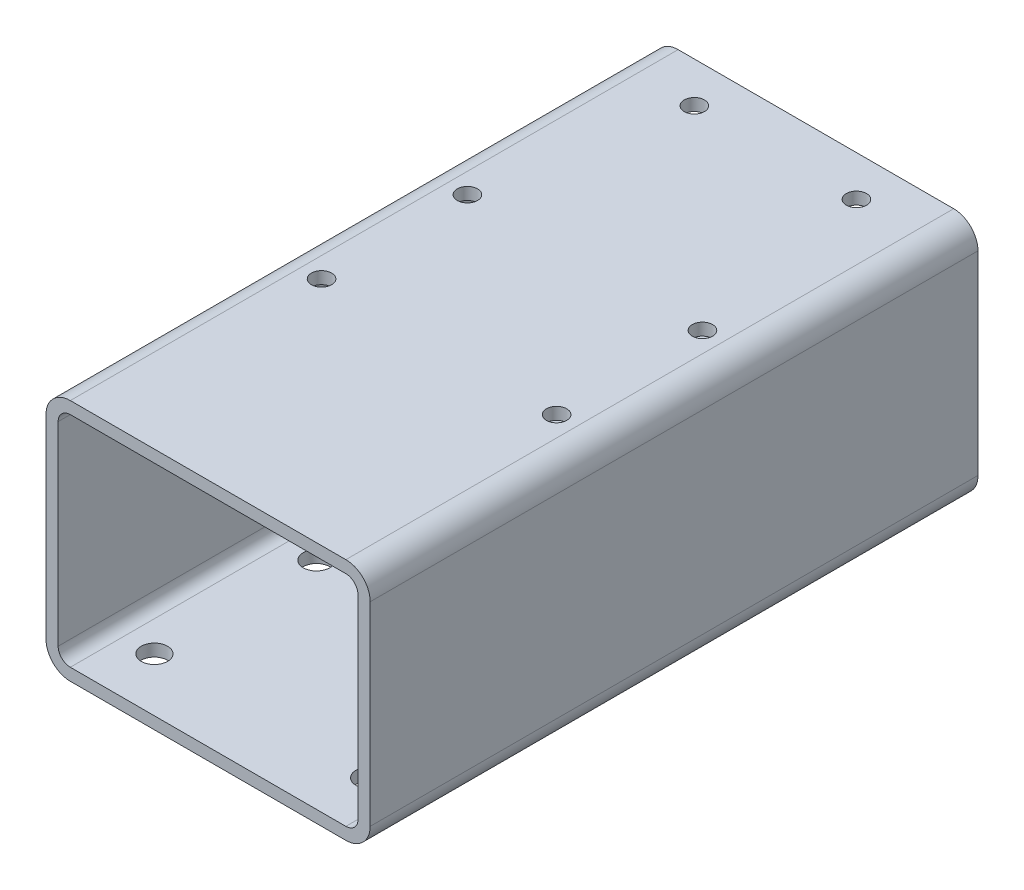
SolidWorks part; units mm, degrees
ref_plane "Front Plane" through (0, 0, 0) normal (0, 0, 1) x (1, 0, 0)
ref_plane "Top Plane" through (0, 0, 0) normal (0, 1, 0) x (1, 0, 0)
ref_plane "Right Plane" through (0, 0, 0) normal (1, 0, 0) x (0, 0, -1)
sketch "Sketch1" plane through (0, 0, 0) normal (0, 0, 1) x (1, 0, 0)
  line L0 (-34, 27) -> (34, 27)
  line L1 (-34, -30) -> (34, -30)
  line L2 (-40, -24) -> (-40, 24)
  line L3 (-34, 30) -> (34, 30)
  line L4 (40, -24) -> (40, 24)
  line L5 (-40, -30) -> (40, 30) construction
  line L6 (-40, 30) -> (40, -30) construction
  line L7 (37, -24) -> (37, 24)
  line L8 (-34, -27) -> (34, -27)
  line L9 (-37, -24) -> (-37, 24)
  arc A0 (-40, 24) -> (-34, 30) centre (-34, 24) cw
  arc A1 (-34, -30) -> (-40, -24) centre (-34, -24) cw
  arc A2 (34, -30) -> (40, -24) centre (34, -24) ccw
  arc A3 (40, 24) -> (34, 30) centre (34, 24) ccw
  arc A4 (37, 24) -> (34, 27) centre (34, 24) ccw
  arc A5 (34, -27) -> (37, -24) centre (34, -24) ccw
  arc A6 (-34, -27) -> (-37, -24) centre (-34, -24) cw
  arc A7 (-37, 24) -> (-34, 27) centre (-34, 24) cw
  point P0 (0, 0)
  dimension "D1" = 6
  dimension "D2" = 6
  dimension "D3" = 60
  dimension "D4" = 80
  dimension "D5" = 3
extrude "Boss-Extrude1" add sketch "Sketch1" along normal blind 75 and the other way blind 75
sketch "Sketch2" plane through (0, -30, 0) normal (0, -1, 0) x (1, 0, 0)
  line L0 (-34, 0) -> (34, 0) construction
  line L1 (-34, -75) -> (-34, 75) construction
  line L2 (34, -75) -> (34, 75) construction
  line L4 (-26.5, 61.75) -> (26.5, 61.75) construction
  line L5 (-26.5, 61.75) -> (-26.5, 21.75) construction
  line L6 (-26.5, 21.75) -> (26.5, 21.75) construction
  line L7 (26.5, 61.75) -> (26.5, 21.75)
  line L9 (0, 61.75) -> (0, 75) construction
  line L10 (-34, 75) -> (34, 75) construction
  line L11 (0, -61.75) -> (0, -75) construction
  line L12 (-26.5, -21.75) -> (26.5, -21.75) construction
  line L13 (-26.5, -61.75) -> (-26.5, -21.75) construction
  line L14 (-26.5, -61.75) -> (26.5, -61.75) construction
  line L15 (26.5, -61.75) -> (26.5, -21.75)
  dimension "D1" = 40
  dimension "D2" = 53
  dimension "D3" = 13.25
hole_wizard "Ø6.5 (6.5) Diameter Hole1" positions "3DSketch1" profile "Sketch3" hole size "Ø6.5" standard "ANSI Metric" end condition up to next
sketch3d "3DSketch1"
  point P0 (-26.5, -30, 61.75)
  point P3 (26.5, -30, 61.75)
  point P6 (26.5, -30, 21.75)
  point P9 (-26.5, -30, 21.75)
  point P12 (-26.5, -30, -21.75)
  point P15 (26.5, -30, -21.75)
  point P18 (26.5, -30, -61.75)
  point P21 (-26.5, -30, -61.75)
sketch "Sketch3" plane through (-26.5, -30, 61.75) normal (1, 0, 0) x (0, 0, -1)
  line L0 (0, 0) -> (0, 3)
  line L1 (0, 3) -> (3.25, 3)
  line L2 (3.25, 3) -> (3.25, 0)
  line L5 (3.25, 0) -> (0, 0)
  line L11 (0, -6.35) -> (0, 107.95) construction
  dimension "Thru Hole Dia." = 6.5
  dimension "Thru Hole Depth" = 3
sketch "Sketch4" plane through (0, 30, 0) normal (0, 1, 0) x (1, 0, 0)
  line L0 (-660, -24) -> (40, -24) construction
  line L1 (40, -24) -> (40, 24) construction
  line L2 (40, 24) -> (-660, 24) construction
  line L3 (-660, 24) -> (-660, -24) construction
  line L4 (-34, 75) -> (-34, -75)
  line L5 (-34, -75) -> (34, -75)
  line L6 (34, -75) -> (34, 75)
  line L7 (34, 75) -> (-34, 75)
  line L8 (-34, 75) -> (-34, -75)
  line L9 (-34, -75) -> (34, -75)
  line L10 (34, -75) -> (34, 75)
  line L11 (34, 75) -> (-34, 75)
  line L12 (-35, 45) -> (35, 45)
  line L13 (35, 45) -> (35, 75)
  line L14 (35, 75) -> (-35, 75)
  line L15 (-35, 75) -> (-35, 45)
  line L16 (-35, 45) -> (35, 45)
  line L17 (35, 45) -> (35, 75)
  line L18 (35, 75) -> (-35, 75)
  line L19 (-35, 75) -> (-35, 45)
  line L20 (-35, 45) -> (35, 45) construction
  line L21 (35, 45) -> (35, 75) construction
  line L22 (35, 75) -> (-35, 75) construction
  line L23 (-35, 75) -> (-35, 45) construction
  line L24 (-660, -24) -> (40, -24)
  line L25 (40, -24) -> (40, 24)
  line L26 (40, 24) -> (-660, 24)
  line L27 (-660, 24) -> (-660, -24)
  line L28 (-35, 45) -> (35, 45)
  line L29 (35, 45) -> (35, 75)
  line L30 (35, 75) -> (-35, 75)
  line L31 (-35, 75) -> (-35, 45)
  circle A1 centre (-591, 18) radius 3.25
  circle A2 centre (-591, 18) radius 3.25
  circle A3 centre (-649, -18) radius 3.25
  circle A4 centre (-649, -18) radius 3.25
  circle A5 centre (-29, -18) radius 3.25
  circle A6 centre (-29, -18) radius 3.25
  circle A7 centre (29, 18) radius 3.25
  circle A8 centre (29, 18) radius 3.25
  circle A9 centre (29, -18) radius 3.25
  circle A10 centre (29, -18) radius 3.25
  circle A11 centre (-29, 18) radius 3.25
  circle A12 centre (-29, 18) radius 3.25
  circle A13 centre (-649, 18) radius 3.25
  circle A14 centre (-649, 18) radius 3.25
  circle A15 centre (-591, -18) radius 3.25
  circle A16 centre (-591, -18) radius 3.25
  circle A17 centre (-20, 65) radius 3.25
  circle A18 centre (-20, 65) radius 3.25
  circle A19 centre (20, 65) radius 3.25
  circle A20 centre (20, 65) radius 3.25
  dimension "D1" = 0
  dimension "D2" = 0
  dimension "D3" = 0
  dimension "D4" = 0
  dimension "D5" = 0
  dimension "D6" = 0
  dimension "D7" = 0
  dimension "D8" = 0
  dimension "D9" = 0
  dimension "D10" = 0
  dimension "D11" = 0
  dimension "D12" = 0
hole_wizard "Tap Drill for M6x1.0 Tap1" positions "3DSketch2" profile "Sketch5" hole size "M6x1.0" standard "ANSI Metric" end condition up to next
sketch3d "3DSketch2"
  point P0 (29, 30, -18)
  point P3 (29, 30, 18)
  point P6 (-29, 30, 18)
  point P9 (-29, 30, -18)
  point P12 (-20, 30, -65)
  point P15 (20, 30, -65)
sketch "Sketch5" plane through (29, 30, -18) normal (1, 0, 0) x (0, 0, 1)
  line L0 (0, 0) -> (0, 3)
  line L1 (0, 3) -> (2.5, 3)
  line L2 (2.5, 3) -> (2.5, 0)
  line L5 (2.5, 0) -> (0, 0)
  line L11 (0, -6.35) -> (0, 107.95) construction
  dimension "Thru Hole Dia." = 5
  dimension "Thru Hole Depth" = 3
